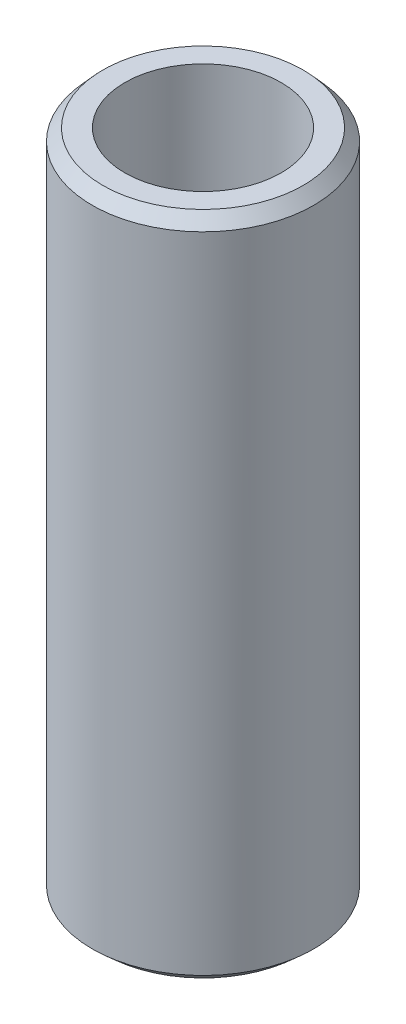
SolidWorks part; units mm, degrees
ref_plane "Front Plane" through (0, 0, 0) normal (0, 0, 1) x (1, 0, 0)
ref_plane "Top Plane" through (0, 0, 0) normal (0, 1, 0) x (1, 0, 0)
ref_plane "Right Plane" through (0, 0, 0) normal (1, 0, 0) x (0, 0, -1)
sketch "Sketch1" plane through (0, 0, 0) normal (0, 1, 0) x (1, 0, 0)
  circle A0 centre (0, 0) radius 20
  dimension "SHAFT_OD" = 40
extrude "Boss-Extrude1" add sketch "Sketch1" along normal blind 120.3795
sketch "Sketch2" plane through (0, 0, 0) normal (0, 1, 0) x (1, 0, 0)
  circle A0 centre (0, 0) radius 14.1314
  dimension "BORE_D" = 28.2628
extrude "Cut-Extrude1" cut sketch "Sketch2" along normal through all
chamfer "Chamfer1" distance 2.1475 angle 41.77 2 edges at (0, 120.3795, 20) (0, 0, 20) first distance on face at (0, 120.3795, 20) first distance on face at (0, 0, 14.1314)
